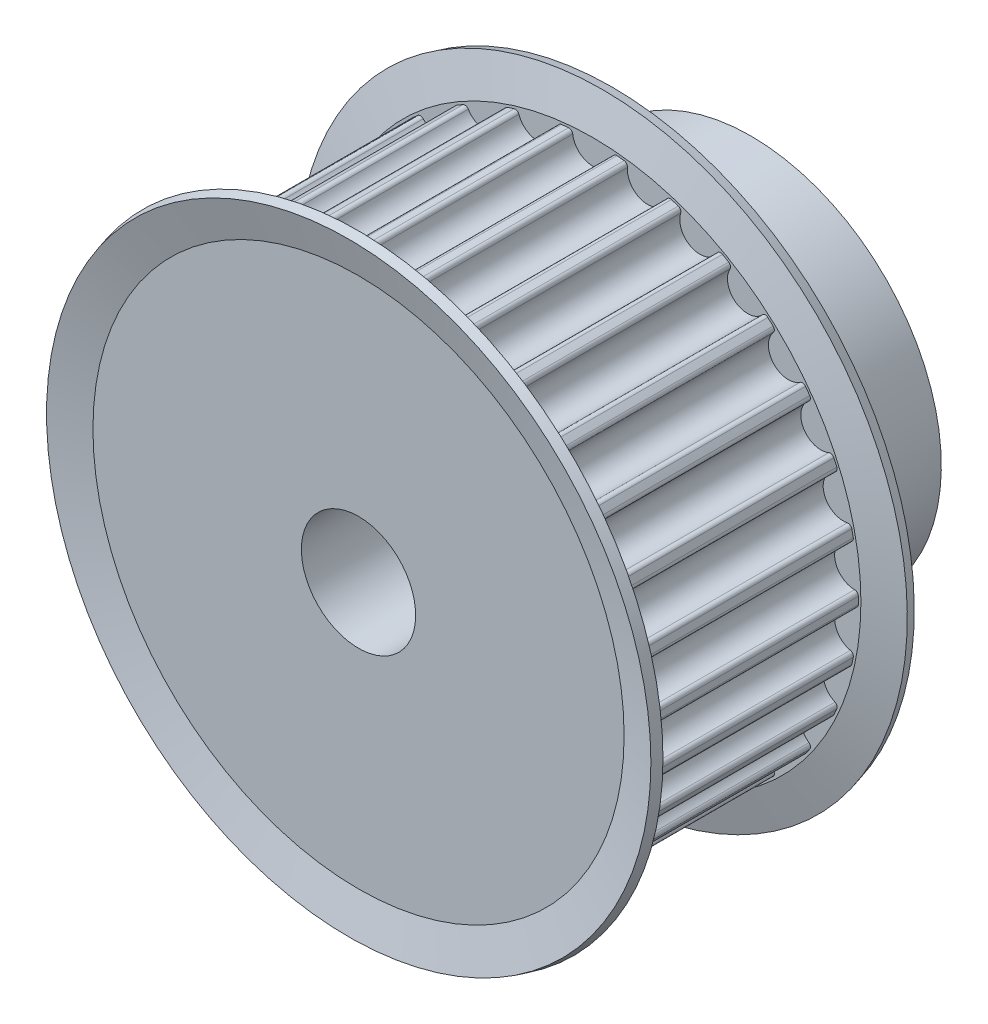
SolidWorks part; units mm, degrees
ref_plane "Front" through (0, 0, 0) normal (0, 0, 1) x (1, 0, 0)
ref_plane "Top" through (0, 0, 0) normal (0, 1, 0) x (1, 0, 0)
ref_plane "Right" through (0, 0, 0) normal (1, 0, 0) x (0, 0, -1)
sketch "support-front-body" plane through (0, 0, 0) normal (0, 0, 1) x (1, 0, 0)
  line L0 (0, 0) -> (0, 13.945) construction
  line L1 (0, 0) -> (0, -13.945) construction
  line L2 (0, 0) -> (13.945, 0) construction
  line L3 (0, 0) -> (-13.945, 0) construction
  circle A0 centre (0, 0) radius 13.945
  dimension "diam-outer" = 27.89
sketch "support-right-body" plane through (0, 0, 0) normal (1, 0, 0) x (0, 0, -1)
  line L0 (0, 0) -> (12.8, 0) construction
  line L1 (0, 13.945) -> (12.8, 13.945)
  line L2 (0, 13.945) -> (0, -13.945)
  line L3 (0, -13.945) -> (12.8, -13.945)
  line L4 (12.8, 13.945) -> (12.8, -13.945)
  dimension "width" = 12.8
sketch "support-right-hub" plane through (0, 0, 0) normal (1, 0, 0) x (0, 0, -1)
  line L0 (20.6, 0) -> (12.8, 0) construction
  line L1 (12.8, 10) -> (20.6, 10)
  line L2 (12.8, 10) -> (12.8, -10)
  line L3 (12.8, -10) -> (20.6, -10)
  line L4 (20.6, 10) -> (20.6, -10)
  line L5 (12.8, 13.945) -> (12.8, -13.945) construction
  line L6 (0, 0) -> (12.8, 0) construction
  line L8 (0, 13.945) -> (0, -13.945) construction
  dimension "diam-hub" = 20
  dimension "dist-hub" = 20.6
sketch "support-right-bore" plane through (0, 0, 0) normal (1, 0, 0) x (0, 0, -1)
  line L0 (0, 13.945) -> (0, -13.945) construction
  line L1 (0, 3) -> (20.6, 3)
  line L2 (0, 3) -> (0, -3)
  line L3 (0, -3) -> (20.6, -3)
  line L4 (20.6, 10) -> (20.6, -10) construction
  line L5 (20.6, 0) -> (0, 0) construction
  line L6 (0, 0) -> (12.8, 0) construction
  line L7 (20.6, 3) -> (20.6, -3)
  line L8 (20.6, -3) -> (20.6, 3) construction
  dimension "diam-bore" = 6
sketch "support-front-tooth" plane through (0, 0, 0) normal (0, 0, 1) x (1, 0, 0)
  line L0 (0, 0) -> (0, 15.185) construction
  line L2 (-1.2711, 15.185) -> (1.2711, 15.185)
  line L3 (1.2711, 15.185) -> (1.2711, 13.8869)
  line L4 (-1.2711, 15.185) -> (-1.2711, 13.8869)
  line L5 (-1.5, 15.185) -> (1.5, 15.185) construction
  line L6 (1.2711, 13.8869) -> (1.5, 15.185) construction
  line L7 (0, 13.945) -> (0, 12.775) construction
  line L8 (0, 13.945) -> (1.2711, 13.945) construction
  line L9 (1.2711, 13.945) -> (0, 13.8338) construction
  circle A0 centre (0, 0) radius 13.945
  circle A1 centre (0, 0) radius 13.945 construction
  arc A3 (1.2711, 13.8869) -> (1.0514, 13.709) centre (1.2526, 13.6851) ccw
  arc A4 (1.0514, 13.709) -> (-1.0514, 13.709) centre (0, 13.8338) cw
  arc A5 (-1.2711, 13.8869) -> (-1.0514, 13.709) centre (-1.2526, 13.6851) cw
  dimension "D2" = 10
  dimension "D4" = 5
  dimension "pitch" = 3
  dimension "height-tooth-inner" = 1.17
  dimension "height-tooth-outer" = 2.41
sketch "support-right-flange" plane through (0, 0, 0) normal (1, 0, 0) x (0, 0, -1)
  line L0 (0, 12.1362) -> (0, 13.945)
  line L1 (12.8, 13.945) -> (12.8, -13.945) construction
  line L2 (0, 13.945) -> (0.5, 13.945) construction
  line L3 (0.5, 14.079) -> (-0.0147, 16)
  line L4 (-0.5147, 15.866) -> (-0.0147, 16)
  line L5 (0.5, 14.079) -> (0.5, 12.1362)
  line L6 (0.5, 12.1362) -> (0, 12.1362)
  line L7 (6.4, 13.945) -> (6.4, 0) construction
  line L8 (0, 13.945) -> (12.8, 13.945) construction
  line L9 (0, 13.945) -> (-0.5147, 15.866)
  line L10 (12.3, 12.1363) -> (12.8, 12.1363)
  line L11 (12.3, 14.079) -> (12.3, 12.1363)
  line L12 (13.3147, 15.866) -> (12.8147, 16)
  line L13 (12.3, 14.079) -> (12.8147, 16)
  line L14 (12.8, 13.945) -> (13.3147, 15.866)
  line L15 (12.8, 12.1363) -> (12.8, 13.945)
  line L16 (12.8, 0) -> (0, 0) construction
  line L17 (12.8, -12.1363) -> (12.8, -13.945)
  line L18 (12.8, -13.945) -> (13.3147, -15.866)
  line L19 (12.3, -14.079) -> (12.8147, -16)
  line L20 (13.3147, -15.866) -> (12.8147, -16)
  line L21 (12.3, -14.079) -> (12.3, -12.1363)
  line L22 (12.3, -12.1363) -> (12.8, -12.1363)
  line L23 (0.5, -12.1363) -> (0, -12.1363)
  line L24 (0.5, -14.079) -> (0.5, -12.1363)
  line L25 (-0.5147, -15.866) -> (-0.0147, -16)
  line L26 (0.5, -14.079) -> (-0.0147, -16)
  line L27 (0, -13.945) -> (-0.5147, -15.866)
  line L28 (0, -12.1363) -> (0, -13.945)
  line L29 (0, 0) -> (12.8, 0) construction
  line L30 (0, 13.945) -> (0.5, 14.079) construction
  line L31 (0.25, 12.1362) -> (0.25, 13.0406) construction
  line L32 (0.25, 13.0406) -> (0.25, 13.945) construction
  line L33 (-0.2647, 15.933) -> (0.25, 14.012) construction
  line L34 (0, 13.945) -> (12.8, 13.945) construction
  line L35 (0, 13.945) -> (0, -13.945) construction
  dimension "angle-flange" = 15
  dimension "thickness-flange" = 0.5
  dimension "diam-flange-inner" = 24.2725
  dimension "diam-flange-outer" = 32
  dimension "diam-flange-angle" = 27.89
ref_axis "ref-axis-center" through (0, 0, -12.8) along (0, 0, 1)
ref_plane "ref-plane-front" through (0, 0, 0) normal (0, 0, 1) x (1, 0, 0)
ref_plane "ref-plane-back" through (0, 0, -12.8) normal (0, 0, 1) x (1, 0, 0)
ref_plane "ref-plane-hub-front" through (0, 0, -12.8) normal (0, 0, 1) x (1, 0, 0)
ref_plane "ref-plane-hub-back" through (0, 0, -20.6) normal (0, 0, 1) x (1, 0, 0)
ref_plane "ref-plane-bore-front" through (0, 0, 0) normal (0, 0, 1) x (1, 0, 0)
ref_plane "ref-plane-bore-back" through (0, 0, -20.6) normal (0, 0, 1) x (1, 0, 0)
sketch "Sketch5" plane through (0, 0, 0) normal (1, 0, 0) x (0, 0, -1)
  line L0 (12.8, 13.945) -> (12.8, -13.945) construction
  line L1 (0, 13.945) -> (12.8, 13.945) construction
  line L2 (0, 13.945) -> (0, -13.945) construction
  line L3 (0, 0) -> (12.8, 0) construction
  line L4 (12.8, 13.945) -> (12.8, 0)
  line L5 (0, 13.945) -> (12.8, 13.945)
  line L6 (0, 13.945) -> (0, 0)
  line L7 (0, 0) -> (12.8, 0) construction
  line L8 (0, 0) -> (12.8, 0)
  dimension "D1" = 13.945
  dimension "D2" = 12.8
revolve "body" add sketch "Sketch5" angle 360 about L7
sketch "Sketch16" plane through (0, 0, 0) normal (1, 0, 0) x (0, 0, -1)
  line L0 (20.6, 10) -> (20.6, -10) construction
  line L1 (12.8, 10) -> (20.6, 10) construction
  line L2 (20.6, 0) -> (12.8, 0) construction
  line L3 (12.8, 10) -> (12.8, -10) construction
  line L4 (20.6, 10) -> (20.6, 0)
  line L5 (12.8, 10) -> (20.6, 10)
  line L6 (20.6, 0) -> (12.8, 0) construction
  line L7 (12.8, 10) -> (12.8, 0)
  line L8 (20.6, 0) -> (12.8, 0)
  dimension "D1" = 7.8
revolve "body-hub" add sketch "Sketch16" angle 360 about L6
sketch "Sketch17" plane through (0, 0, 0) normal (1, 0, 0) x (0, 0, -1)
  line L1 (20.6, 0) -> (0, 0) construction
  line L2 (0, 3) -> (20.6, 3) construction
  line L3 (0, 3) -> (0, -3) construction
  line L4 (20.6, 3) -> (20.6, -3) construction
  line L5 (20.6, 0) -> (0, 0) construction
  line L6 (0, 3) -> (20.6, 3)
  line L7 (0, 3) -> (0, 0)
  line L8 (20.6, 0) -> (0, 0)
  line L9 (20.6, 3) -> (20.6, 0)
revolve "body-bore" cut sketch "Sketch17" angle 360 about L5
sketch "Sketch23" plane through (0, 0, 0) normal (0, 0, 1) x (1, 0, 0)
  line L3 (1.2711, 13.8869) -> (1.2711, 15.185)
  line L4 (1.2711, 15.185) -> (-1.2711, 15.185)
  line L5 (-1.2711, 15.185) -> (-1.2711, 13.8869)
  line L6 (1.2711, 13.8869) -> (1.2711, 15.185)
  line L7 (1.2711, 15.185) -> (-1.2711, 15.185)
  line L8 (-1.2711, 15.185) -> (-1.2711, 13.8869)
  arc A3 (1.2711, 13.8869) -> (1.0514, 13.709) centre (1.2526, 13.6851) ccw
  arc A4 (-1.0514, 13.709) -> (-1.2711, 13.8869) centre (-1.2526, 13.6851) ccw
  arc A5 (-1.0514, 13.709) -> (1.0514, 13.709) centre (0, 13.8338) ccw
  arc A6 (1.2711, 13.8869) -> (1.0514, 13.709) centre (1.2526, 13.6851) ccw
  arc A7 (-1.0514, 13.709) -> (-1.2711, 13.8869) centre (-1.2526, 13.6851) ccw
  arc A8 (-1.0514, 13.709) -> (1.0514, 13.709) centre (0, 13.8338) ccw
  dimension "D1" = 0
extrude "cut-tooth" cut sketch "Sketch23" against normal up to surface (12.8 mm away) up to plane "ref-plane-back"
pattern_circular "pattern-tooth" count 30 over 360 about axis through (0, 0, -12.8) along (0, 0, 1) of "cut-tooth"
sketch "Sketch25" plane through (0, 0, 0) normal (1, 0, 0) x (0, 0, -1)
  line L0 (0, 0) -> (12.8, 0) construction
  line L1 (0.5, 12.1362) -> (0, 12.1362) construction
  line L2 (0.5, 14.079) -> (0.5, 12.1362) construction
  line L4 (-0.5147, 15.866) -> (-0.0147, 16) construction
  line L5 (0, 13.945) -> (-0.5147, 15.866) construction
  line L6 (0, 12.1362) -> (0, 13.945) construction
  line L7 (0, 0) -> (12.8, 0) construction
  line L8 (0.5, 12.1362) -> (0, 12.1362)
  line L9 (0.5, 14.079) -> (0.5, 12.1362)
  line L10 (-0.5147, 15.866) -> (-0.0147, 16)
  line L11 (0.5, 14.079) -> (-0.0147, 16) construction
  line L12 (0, 13.945) -> (-0.5147, 15.866)
  line L13 (0, 12.1362) -> (0, 13.945)
  line L14 (0.5, 14.079) -> (-0.0147, 16)
revolve "body-flange-front" add sketch "Sketch25" angle 360 about L7
sketch "Sketch26" plane through (0, 0, 0) normal (1, 0, 0) x (0, 0, -1)
  line L0 (12.8, 0) -> (0, 0) construction
  line L1 (12.3, 12.1363) -> (12.8, 12.1363) construction
  line L2 (12.3, 14.079) -> (12.3, 12.1363) construction
  line L4 (13.3147, 15.866) -> (12.8147, 16) construction
  line L5 (12.8, 13.945) -> (13.3147, 15.866) construction
  line L6 (12.8, 12.1363) -> (12.8, 13.945) construction
  line L7 (12.8, 0) -> (0, 0) construction
  line L8 (12.3, 12.1363) -> (12.8, 12.1363)
  line L9 (12.3, 14.079) -> (12.3, 12.1363)
  line L10 (13.3147, 15.866) -> (12.8147, 16)
  line L11 (12.3, 14.079) -> (12.8147, 16) construction
  line L12 (12.8, 13.945) -> (13.3147, 15.866)
  line L13 (12.8, 12.1363) -> (12.8, 13.945)
  line L14 (12.3, 14.079) -> (12.8147, 16)
revolve "body-flange-back" add sketch "Sketch26" angle 360 about L7
equation "\"diam-flange-angle@support-right-flange\" = \"diam-outer@support-front-body\""
equation "\"diam-flange-inner@support-right-flange\"=(\"diam-outer@support-front-body\" - 2 * \"height-tooth-inner@support-front-tooth\" )  * 0.95"
